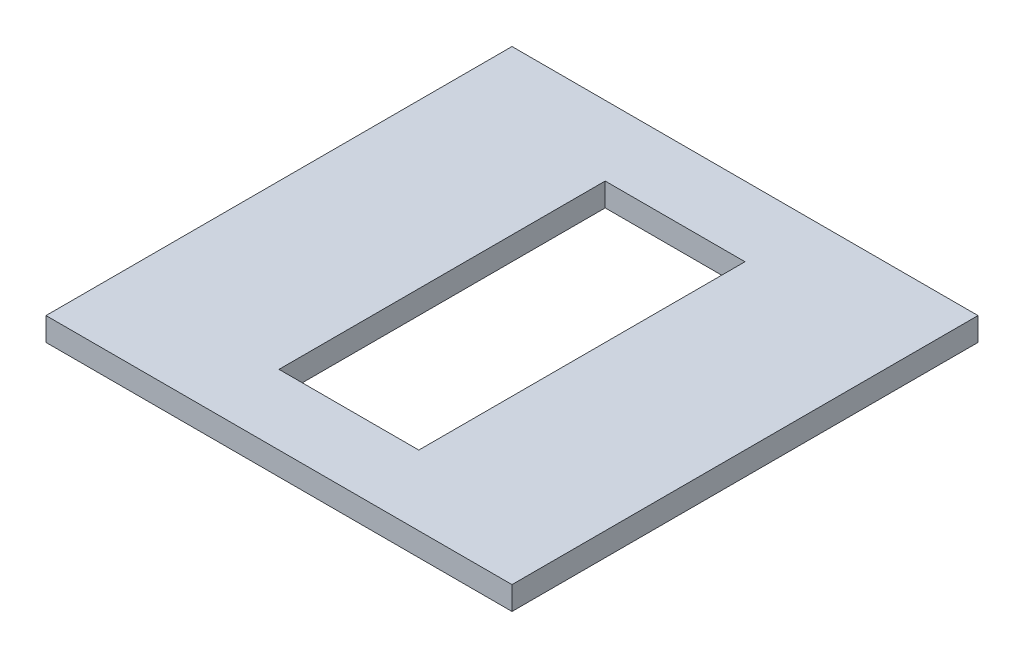
SolidWorks part; units mm, degrees
ref_plane "Front Plane" through (0, 0, 0) normal (0, 0, 1) x (1, 0, 0)
ref_plane "Top Plane" through (0, 0, 0) normal (0, 1, 0) x (1, 0, 0)
ref_plane "Right Plane" through (0, 0, 0) normal (1, 0, 0) x (0, 0, -1)
sketch "Sketch1" plane through (0, 0, 0) normal (0, 1, 0) x (1, 0, 0)
  line L1 (-49.3023, 40.5814) -> (50.6977, 40.5814)
  line L2 (-49.3023, 40.5814) -> (-49.3023, -59.4186)
  line L3 (-49.3023, -59.4186) -> (50.6977, -59.4186)
  line L4 (50.6977, 40.5814) -> (50.6977, -59.4186)
  line L5 (-14.3023, 25.5814) -> (15.6977, 25.5814)
  line L6 (-14.3023, 25.5814) -> (-14.3023, -44.4186)
  line L7 (-14.3023, -44.4186) -> (15.6977, -44.4186)
  line L8 (15.6977, 25.5814) -> (15.6977, -44.4186)
  dimension "D1" = 100
  dimension "D2" = 100
  dimension "D3" = 30
  dimension "D4" = 70
  dimension "D5" = 15
  dimension "D6" = 35
extrude "Boss-Extrude1" add sketch "Sketch1" along normal blind 5
